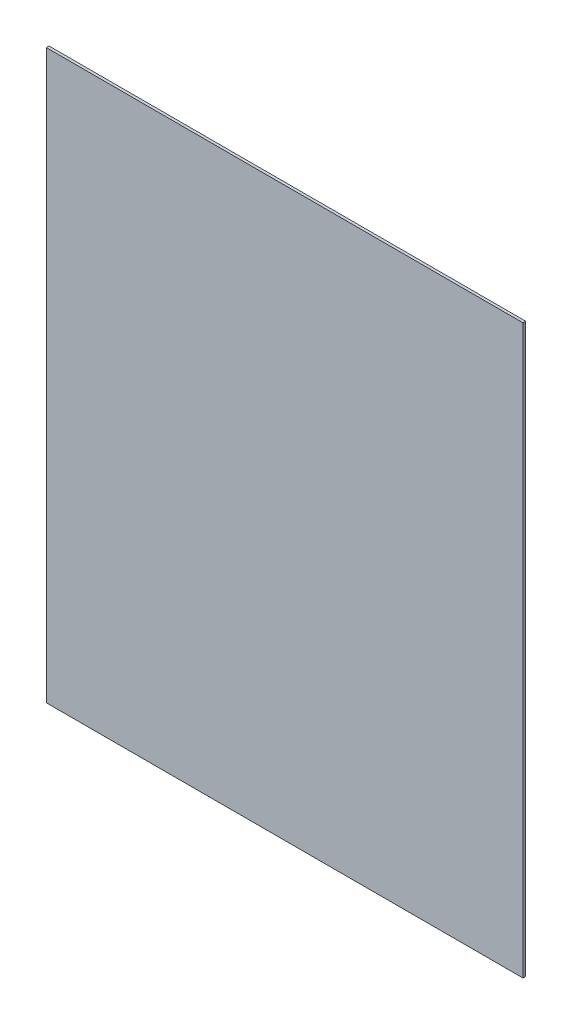
SolidWorks part; units mm, degrees
ref_plane "Ön Düzlem" through (0, 0, 0) normal (0, 0, 1) x (1, 0, 0)
ref_plane "Üst Düzlem" through (0, 0, 0) normal (0, 1, 0) x (1, 0, 0)
ref_plane "Sağ Düzlem" through (0, 0, 0) normal (1, 0, 0) x (0, 0, -1)
sketch "Çizim1" plane through (0, 0, 0) normal (0, 0, 1) x (1, 0, 0)
  line L1 (0, 0) -> (2100, 0)
  line L2 (0, 0) -> (0, 2500)
  line L3 (0, 2500) -> (2100, 2500)
  line L4 (2100, 0) -> (2100, 2500)
  dimension "D1" = 2500
  dimension "D2" = 2100
base flange "Taban-Flanş1" sketch "Çizim1" thickness 12 reverse thickness direction no parameters "D1"=4
sketch "Büküm-Çizgileri1" [suppressed] plane through (0, 0, 0) normal (0, 1, 0) x (1, 0, 0)
sketch "Sınırlandırma-Kutusu1" [suppressed] plane through (0, 0, 0) normal (0, 1, 0) x (1, 0, 0)
sheet metal parameters "Sac-Levha1" thickness 12 parameters "D1"=4
flat pattern "Düz-Çoğaltma1" [suppressed]
sketch "Büküm-Çizgileri2" plane through (0, 0, 0) normal (0, 1, 0) x (1, 0, 0)
sketch3d "Sınırlandırma-Kutusu2" [suppressed]
  line L0 (2100, 2500, 0) -> (2100, 0, 0) construction
  line L1 (0, 2500, 0) -> (0, 0, 0) construction
  line L2 (2100, 2500, 0) -> (0, 2500, 0) construction
  line L3 (2100, 0, 0) -> (0, 0, 0) construction
